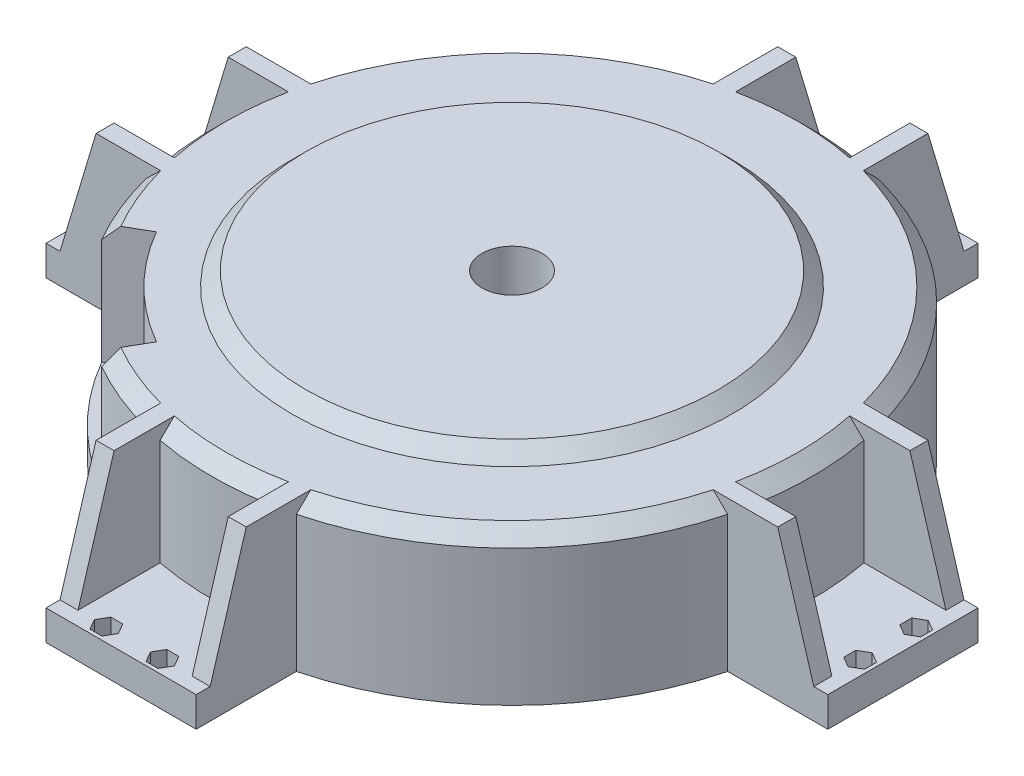
SolidWorks part; units mm, degrees
ref_plane "Front Plane" through (0, 0, 0) normal (0, 0, 1) x (1, 0, 0)
ref_plane "Top Plane" through (0, 0, 0) normal (0, 1, 0) x (1, 0, 0)
ref_plane "Right Plane" through (0, 0, 0) normal (1, 0, 0) x (0, 0, -1)
sketch "Sketch2" plane through (0, 0, 0) normal (0, 1, 0) x (1, 0, 0)
  line L0 (-14.25, -94.12) -> (-14.25, -73.6338)
  line L1 (94.12, 14.25) -> (94.12, 18.75)
  line L2 (97.62, 0) -> (97.62, 18.75)
  line L3 (97.62, 18.75) -> (72.6184, 18.75)
  line L5 (72.6184, -18.75) -> (97.62, -18.75)
  line L6 (97.62, -18.75) -> (97.62, 0)
  line L7 (94.12, -18.75) -> (94.12, -14.25)
  line L8 (94.12, -14.25) -> (73.6338, -14.25)
  line L9 (94.12, 14.25) -> (73.6338, 14.25)
  line L10 (-18.75, -72.6184) -> (-18.75, -97.62)
  line L11 (-18.75, -97.62) -> (0, -97.62)
  line L12 (-18.75, -94.12) -> (-14.25, -94.12)
  line L13 (8.3239, -96.7161) -> (5.3239, -96.72)
  line L14 (5.3239, -96.72) -> (3.8206, -94.1239)
  line L15 (3.8206, -94.1239) -> (5.3172, -91.5239)
  line L16 (5.3172, -91.5239) -> (8.3172, -91.52)
  line L17 (8.3172, -91.52) -> (9.8206, -94.1161)
  line L18 (9.8206, -94.1161) -> (8.3239, -96.7161)
  line L19 (-5.6828, -96.72) -> (-4.1794, -94.1239)
  line L20 (-4.1794, -94.1239) -> (-5.6761, -91.5239)
  line L21 (-5.6761, -91.5239) -> (-8.6761, -91.52)
  line L22 (-8.6761, -91.52) -> (-10.1794, -94.1161)
  line L23 (-10.1794, -94.1161) -> (-8.6828, -96.7161)
  line L24 (-8.6828, -96.7161) -> (-5.6828, -96.72)
  line L25 (14.25, -94.12) -> (14.25, -73.6338)
  line L26 (18.75, -97.62) -> (18.75, -72.6184)
  line L27 (14.25, -94.12) -> (18.75, -94.12)
  line L28 (0, -97.62) -> (18.75, -97.62)
  line L29 (-94.12, 14.25) -> (-73.6338, 14.25)
  line L30 (-72.6184, 18.75) -> (-97.62, 18.75)
  line L31 (-97.62, 18.75) -> (-97.62, 0)
  line L32 (-94.12, 18.75) -> (-94.12, 14.25)
  line L33 (-96.7161, -8.3239) -> (-96.72, -5.3239)
  line L34 (96.72, -5.6828) -> (94.1239, -4.1794)
  line L35 (-96.72, -5.3239) -> (-94.1239, -3.8206)
  line L36 (-94.1239, -3.8206) -> (-91.5239, -5.3172)
  line L37 (94.1239, -4.1794) -> (91.5239, -5.6761)
  line L38 (91.5239, -5.6761) -> (91.52, -8.6761)
  line L39 (91.52, -8.6761) -> (94.1161, -10.1794)
  line L40 (94.1161, -10.1794) -> (96.7161, -8.6828)
  line L41 (96.7161, -8.6828) -> (96.72, -5.6828)
  line L42 (-91.5239, -5.3172) -> (-91.52, -8.3172)
  line L43 (96.7161, 8.3239) -> (96.72, 5.3239)
  line L44 (94.1161, 9.8206) -> (96.7161, 8.3239)
  line L45 (91.52, 8.3172) -> (94.1161, 9.8206)
  line L46 (91.5239, 5.3172) -> (91.52, 8.3172)
  line L47 (94.1239, 3.8206) -> (91.5239, 5.3172)
  line L48 (96.72, 5.3239) -> (94.1239, 3.8206)
  line L49 (-91.52, -8.3172) -> (-94.1161, -9.8206)
  line L50 (-94.1161, -9.8206) -> (-96.7161, -8.3239)
  line L51 (-96.72, 5.6828) -> (-94.1239, 4.1794)
  line L52 (-94.1239, 4.1794) -> (-91.5239, 5.6761)
  line L53 (-91.5239, 5.6761) -> (-91.52, 8.6761)
  line L54 (-91.52, 8.6761) -> (-94.1161, 10.1794)
  line L55 (-94.1161, 10.1794) -> (-96.7161, 8.6828)
  line L56 (-96.7161, 8.6828) -> (-96.72, 5.6828)
  line L57 (-94.12, -14.25) -> (-73.6338, -14.25)
  line L58 (-97.62, -18.75) -> (-72.6184, -18.75)
  line L59 (-94.12, -14.25) -> (-94.12, -18.75)
  line L60 (-97.62, 0) -> (-97.62, -18.75)
  line L61 (14.25, 94.12) -> (14.25, 73.6338)
  line L62 (18.75, 72.6184) -> (18.75, 97.62)
  line L63 (18.75, 97.62) -> (0, 97.62)
  line L64 (18.75, 94.12) -> (14.25, 94.12)
  line L65 (-8.3239, 96.7161) -> (-5.3239, 96.72)
  line L66 (-5.3239, 96.72) -> (-3.8206, 94.1239)
  line L67 (-3.8206, 94.1239) -> (-5.3172, 91.5239)
  line L68 (-5.3172, 91.5239) -> (-8.3172, 91.52)
  line L69 (-8.3172, 91.52) -> (-9.8206, 94.1161)
  line L70 (-9.8206, 94.1161) -> (-8.3239, 96.7161)
  line L71 (5.6828, 96.72) -> (4.1794, 94.1239)
  line L72 (4.1794, 94.1239) -> (5.6761, 91.5239)
  line L73 (5.6761, 91.5239) -> (8.6761, 91.52)
  line L74 (8.6761, 91.52) -> (10.1794, 94.1161)
  line L75 (10.1794, 94.1161) -> (8.6828, 96.7161)
  line L76 (8.6828, 96.7161) -> (5.6828, 96.72)
  line L77 (-14.25, 94.12) -> (-14.25, 73.6338)
  line L78 (-18.75, 97.62) -> (-18.75, 72.6184)
  line L79 (-14.25, 94.12) -> (-18.75, 94.12)
  line L80 (0, 97.62) -> (-18.75, 97.62)
  line L81 (-73.6338, 14.25) -> (-73.6338, -14.25)
  line L82 (-14.25, 73.6338) -> (14.25, 73.6338)
  line L83 (73.6338, 14.25) -> (73.6338, -14.25)
  line L84 (14.25, -73.6338) -> (-14.25, -73.6338)
  arc A0 (-72.6184, -18.75) -> (-18.75, -72.6184) centre (0, 0) ccw
  circle A1 centre (94.12, -7.1794) radius 2.5981 construction
  arc A2 (72.6184, 18.75) -> (18.75, 72.6184) centre (0, 0) ccw
  arc A3 (-18.75, 72.6184) -> (-72.6184, 18.75) centre (0, 0) ccw
  arc A4 (18.75, -72.6184) -> (72.6184, -18.75) centre (0, 0) ccw
  point P50 (0, 0)
  point P101 (0, 0)
  dimension "D1" = 150
  dimension "D2" = 4
  dimension "D5" = 4.5
extrude "Boss-Extrude1" add sketch "Sketch2" along normal blind 37.5 contours A4 L5 L6 L2 L3 A2 L62 L63 L80 L78 A3 L30 L31 L60 L58 A0 L10 L11 L28 L26 | L19 L20 L21 L22 L23 L24 | L13 L14 L15 L16 L17 L18 | L34 L37 L38 L39 L40 L41 | L43 L48 L47 L46 L45 L44 | L33 L35 L36 L42 L49 L50 | L51 L52 L53 L54 L55 L56 | L71 L72 L73 L74 L75 L76 | L65 L66 L67 L68 L69 L70
sketch "Sketch4" plane through (0, 0, 18.75) normal (0, 0, 1) x (1, 0, 0)
  line L0 (-97.62, 37.5) -> (-94.12, 37.5)
  line L1 (-97.62, 37.5) -> (-72.6184, 37.5) construction
  line L2 (-94.12, 37.5) -> (-94.12, 7.5)
  line L3 (-94.12, 7.5) -> (-97.62, 7.5)
  line L4 (-97.62, 37.5) -> (-97.62, 0) construction
  line L5 (-97.62, 7.5) -> (-97.62, 37.5)
  dimension "D1" = 3.5
extrude "Cut-Extrude1" cut sketch "Sketch4" against normal blind 37.5
sketch "Sketch7" plane through (18.75, 0, 0) normal (1, 0, 0) x (0, 0, -1)
  line L0 (-97.62, 37.5) -> (-94.12, 37.5)
  line L1 (-97.62, 37.5) -> (-72.6184, 37.5) construction
  line L2 (-94.12, 37.5) -> (-94.12, 7.5)
  line L3 (-94.12, 7.5) -> (-97.62, 7.5)
  line L4 (-97.62, 37.5) -> (-97.62, 0) construction
  line L5 (-97.62, 7.5) -> (-97.62, 37.5)
extrude "Cut-Extrude3" cut sketch "Sketch7" against normal through all
ref_plane "Plane1" through (0, 0, 0) normal (0, 0, 1) x (1, 0, 0)
mirror "Mirror1" about plane through (0, 0, 0) normal (0, 0, 1) of "Cut-Extrude3"
ref_plane "Plane2" through (0, 0, 0) normal (-1, 0, 0) x (0, 0, 1)
mirror "Mirror2" about plane through (0, 0, 0) normal (-1, 0, 0) of "Cut-Extrude1"
sketch "Sketch8" plane through (0, 37.5, 0) normal (0, 1, 0) x (1, 0, 0)
  line L1 (10.1772, 94.12) -> (18.75, 94.12) construction
  line L3 (-18.75, 94.12) -> (-9.8183, 94.12) construction
  line L5 (-14.25, 94.12) -> (-14.25, 73.6338)
  line L6 (-94.12, 14.25) -> (-94.12, -14.25)
  line L8 (14.25, 94.12) -> (14.25, 73.6338)
  line L9 (-94.12, 18.75) -> (-94.12, 10.1772) construction
  line L11 (-94.12, 14.25) -> (-73.6338, 14.25)
  line L12 (-14.25, 94.12) -> (14.25, 94.12)
  line L13 (-94.12, -9.8183) -> (-94.12, -18.75) construction
  line L14 (-94.12, -14.25) -> (-73.6338, -14.25)
  arc A0 (-73.6338, 14.25) -> (-73.6338, -14.25) centre (0, 0) ccw
  arc A1 (14.25, 73.6338) -> (-14.25, 73.6338) centre (0, 0) ccw
extrude "Cut-Extrude4" cut sketch "Sketch8" against normal blind 30
mirror "Mirror3" about plane through (0, 0, 0) normal (-1, 0, 0) of "Cut-Extrude4" second plane through (0, 0, 0) second plane normal (0, 0, 1)
chamfer "Chamfer1" distance 3.5 angle 45 8 edges at (53.033, 37.5, -53.033) (0, 37.5, -75) (-75, 37.5, 0) (0, 37.5, 75) (-53.033, 37.5, -53.033) (75, 37.5, 0) (-53.033, 37.5, 53.033) (53.033, 37.5, 53.033)
sketch "Sketch9" plane through (18.75, 0, 0) normal (1, 0, 0) x (0, 0, -1)
  line L0 (-72.6184, 34) -> (-72.6184, 37.5)
  line L1 (-94.12, 37.5) -> (-68.9977, 37.5) construction
  line L3 (-85.1184, 37.5) -> (-94.12, 7.5)
  line L4 (-94.12, 7.5) -> (-94.12, 37.5)
  line L5 (-94.12, 37.5) -> (-85.1184, 37.5)
extrude "Cut-Extrude5" cut sketch "Sketch9" against normal through all both and the other way through all contours L3 L4 L5
mirror "Mirror4" about plane through (0, 0, 0) normal (-1, 0, 0) of "Cut-Extrude5" second plane through (0, 0, 0) second plane normal (0, 0, 1)
sketch "Sketch10" plane through (0, 0, 18.75) normal (0, 0, 1) x (1, 0, 0)
  line L1 (-94.12, 37.5) -> (-68.9977, 37.5) construction
  line L3 (-85.1184, 37.5) -> (-94.12, 7.5)
  line L4 (-94.12, 7.5) -> (-94.12, 37.5)
  line L5 (-94.12, 37.5) -> (-85.1184, 37.5)
extrude "Cut-Extrude6" cut sketch "Sketch10" against normal through all both and the other way through all
mirror "Mirror5" about plane through (0, 0, 0) normal (-1, 0, 0) of "Cut-Extrude6"
sketch "Sketch11" plane through (0, 37.5, 0) normal (0, 1, 0) x (1, 0, 0)
  line L0 (-56.2917, -32.5) -> (-64.9519, -37.5)
  line L1 (-32.5, -56.2917) -> (-37.5, -64.9519)
  arc A0 (-72.6184, -18.75) -> (-18.75, -72.6184) centre (0, 0) ccw construction
  arc A1 (-56.2917, -32.5) -> (-32.5, -56.2917) centre (0, 0) ccw
  arc A2 (-64.9519, -37.5) -> (-37.5, -64.9519) centre (0, 0) ccw
  dimension "D1" = 130
extrude "Cut-Extrude7" cut sketch "Sketch11" against normal blind 30 and the other way through all
sketch "Sketch14" plane through (0, 37.5, 0) normal (0, 1, 0) x (1, 0, 0)
  circle A0 centre (0, 0) radius 55
  dimension "D1" = 110
extrude "Boss-Extrude3" add sketch "Sketch14" along normal blind 3.5
chamfer "Chamfer2" distance 3.5 angle 45 1 edges at (0, 41, 55)
sketch "Sketch15" plane through (0, 41, 0) normal (0, 1, 0) x (1, 0, 0)
  circle A1 centre (0, 0) radius 7.5
  dimension "D1" = 15
extrude "Cut-Extrude8" cut sketch "Sketch15" against normal blind 25
